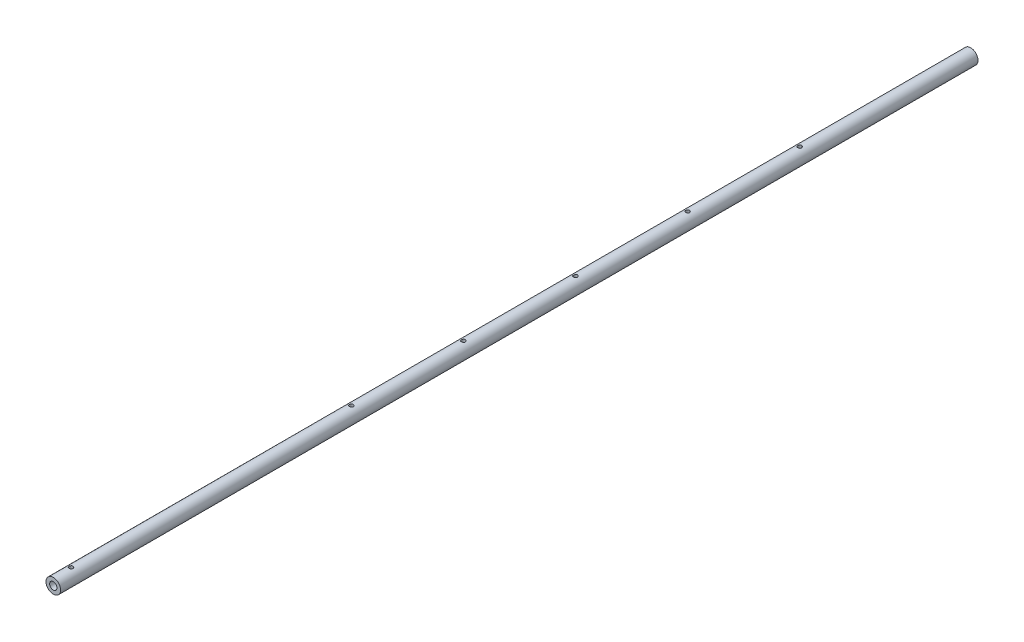
SolidWorks part; units mm, degrees
ref_plane "Front Plane" through (0, 0, 0) normal (0, 0, 1) x (1, 0, 0)
ref_plane "Top Plane" through (0, 0, 0) normal (0, 1, 0) x (1, 0, 0)
ref_plane "Right Plane" through (0, 0, 0) normal (1, 0, 0) x (0, 0, -1)
sketch "Sketch1" plane through (0, 0, 0) normal (0, 0, 1) x (1, 0, 0)
  circle A0 centre (0, 0) radius 3.9306
  circle A1 centre (0, 0) radius 7.8613
  dimension "D1" = 15.7226
  dimension "D2" = 7.8613
extrude "Rod" add sketch "Sketch1" along normal blind 987.425
sketch "Sketch3" plane through (0, 0, 0) normal (0, 1, 0) x (1, 0, 0)
  line L0 (0, -666.75) -> (0, -962.025) construction
  line L1 (-7.8613, -987.425) -> (7.8613, -987.425) construction
  circle A0 centre (0, -184.15) radius 2.1082
  circle A4 centre (0, -304.8) radius 2.1082
  circle A8 centre (0, -425.45) radius 2.1082
  circle A11 centre (0, -546.1) radius 2.1082
  circle A12 centre (0, -666.75) radius 2.1082
  circle A13 centre (0, -968.375) radius 2.1082
  point P13 (0, 0)
  dimension "D1" = 4.2164
  dimension "D6" = 4.2164
  dimension "D2" = 184.15
  dimension "D4" = 120.65
  dimension "D5" = 295.275
  dimension "D7" = 19.05
  dimension "D3" = 5
extrude "Holes" cut sketch "Sketch3" against normal through all both and the other way through all
ref_plane "Handle Location" through (0, 0, 962.025) normal (0, 0, 1) x (1, 0, 0)
equation "\"L\"= 38.875"
equation "\"D1@Rod\" = \"L\""
equation "\"N\"= 5"
equation "\"D3@Sketch3\"=\"N\""
equation "\"S\"= 4.75"
equation "\"D4@Sketch3\"=\"S\""
equation "\"O\"= 7.25"
equation "\"D2@Sketch3\"=\"O\""
equation "\"H\"= 11.625"
equation "\"D5@Sketch3\"=\"H\""
